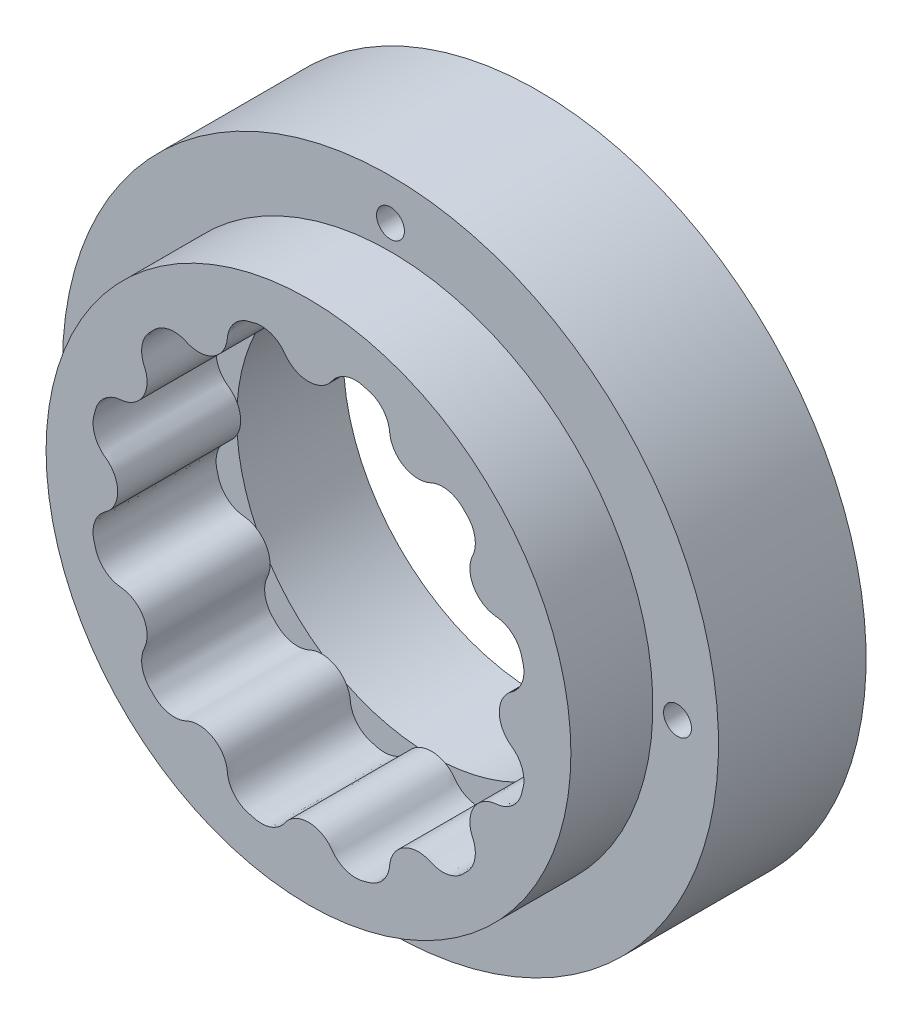
SolidWorks part; units mm, degrees
material "ABS PC"
ref_plane "Front Plane" through (0, 0, 0) normal (0, 0, 1) x (1, 0, 0)
ref_plane "Top Plane" through (0, 0, 0) normal (0, 1, 0) x (1, 0, 0)
ref_plane "Right Plane" through (0, 0, 0) normal (1, 0, 0) x (0, 0, -1)
sketch "Sketch1" plane through (0, 0, 0) normal (0, 0, 1) x (1, 0, 0)
  circle A2 centre (0, 0) radius 32
  spline S0 degree 3 poles (7.3592, -25.9621) (8.807, -25.5517) (9.7655, -24.3915) (9.8952, -22.8922) (9.8952, -22.8915) (9.8953, -22.89) (9.8955, -22.8879) (9.8956, -22.8865) (9.8957, -22.8858) (10.1265, -20.2177) (12.4458, -18.8786) (14.8718, -20.0128) (14.8725, -20.0131) (14.8738, -20.0137) (14.8757, -20.0146) (14.877, -20.0152) (14.8776, -20.0155) (16.2248, -20.6454) (17.6929, -20.4076) (18.7725, -19.3848) (18.7796, -19.3781) (18.7937, -19.3646) (18.8148, -19.3441) (18.8288, -19.3305) (18.8358, -19.3237) (19.0005, -19.1631) (19.1631, -19.0005) (19.3237, -18.8358) (19.3305, -18.8288) (19.3441, -18.8148) (19.3646, -18.7937) (19.3781, -18.7796) (19.3848, -18.7725) (20.4076, -17.6929) (20.6454, -16.2248) (20.0155, -14.8776) (20.0152, -14.877) (20.0146, -14.8757) (20.0137, -14.8738) (20.0131, -14.8725) (20.0128, -14.8718) (18.8786, -12.4458) (20.2177, -10.1265) (22.8858, -9.8957) (22.8865, -9.8956) (22.8879, -9.8955) (22.89, -9.8953) (22.8915, -9.8952) (22.8922, -9.8952) (24.3738, -9.767) (25.5263, -8.8271) (25.9499, -7.4015) (25.9526, -7.3921) (25.9581, -7.3734) (25.9661, -7.3451) (25.9714, -7.3263) (25.9741, -7.3169) (26.0365, -7.0955) (26.096, -6.8733) (26.1527, -6.6504) (26.1551, -6.641) (26.1599, -6.622) (26.1671, -6.5935) (26.1717, -6.5745) (26.174, -6.565) (26.52, -5.1187) (25.9918, -3.7284) (24.7728, -2.8766) (24.7722, -2.8762) (24.771, -2.8754) (24.7693, -2.8742) (24.7681, -2.8734) (24.7675, -2.873) (22.5723, -1.339) (22.5723, 1.339) (24.7675, 2.873) (24.7681, 2.8734) (24.7693, 2.8742) (24.771, 2.8754) (24.7722, 2.8762) (24.7728, 2.8766) (25.9918, 3.7284) (26.52, 5.1187) (26.174, 6.565) (26.1717, 6.5745) (26.1671, 6.5935) (26.1599, 6.622) (26.1551, 6.641) (26.1527, 6.6504) (26.096, 6.8733) (26.0365, 7.0955) (25.9741, 7.3169) (25.9714, 7.3263) (25.9661, 7.3451) (25.9581, 7.3734) (25.9526, 7.3921) (25.9499, 7.4015) (25.5263, 8.8271) (24.3738, 9.767) (22.8922, 9.8952) (22.8915, 9.8952) (22.89, 9.8953) (22.8879, 9.8955) (22.8865, 9.8956) (22.8858, 9.8957) (20.2177, 10.1265) (18.8786, 12.4458) (20.0128, 14.8718) (20.0131, 14.8725) (20.0137, 14.8738) (20.0146, 14.8757) (20.0152, 14.877) (20.0155, 14.8776) (20.6454, 16.2248) (20.4076, 17.6929) (19.3848, 18.7725) (19.3781, 18.7796) (19.3646, 18.7937) (19.3441, 18.8148) (19.3305, 18.8288) (19.3237, 18.8358) (19.1631, 19.0005) (19.0005, 19.1631) (18.8358, 19.3237) (18.8288, 19.3305) (18.8148, 19.3441) (18.7937, 19.3646) (18.7796, 19.3781) (18.7725, 19.3848) (17.6929, 20.4076) (16.2248, 20.6454) (14.8776, 20.0155) (14.877, 20.0152) (14.8757, 20.0146) (14.8738, 20.0137) (14.8725, 20.0131) (14.8718, 20.0128) (12.4458, 18.8786) (10.1265, 20.2177) (9.8957, 22.8858) (9.8956, 22.8865) (9.8955, 22.8879) (9.8953, 22.89) (9.8952, 22.8915) (9.8952, 22.8922) (9.767, 24.3738) (8.8271, 25.5263) (7.4015, 25.9499) (7.3921, 25.9526) (7.3734, 25.9581) (7.3451, 25.9661) (7.3263, 25.9714) (7.3169, 25.9741) (7.0955, 26.0365) (6.8733, 26.096) (6.6504, 26.1527) (6.641, 26.1551) (6.622, 26.1599) (6.5935, 26.1671) (6.5745, 26.1717) (6.565, 26.174) (5.1187, 26.52) (3.7284, 25.9918) (2.8766, 24.7728) (2.8762, 24.7722) (2.8754, 24.771) (2.8742, 24.7693) (2.8734, 24.7681) (2.873, 24.7675) (1.339, 22.5723) (-1.339, 22.5723) (-2.873, 24.7675) (-2.8734, 24.7681) (-2.8742, 24.7693) (-2.8754, 24.771) (-2.8762, 24.7722) (-2.8766, 24.7728) (-3.7284, 25.9918) (-5.1187, 26.52) (-6.565, 26.174) (-6.5745, 26.1717) (-6.5935, 26.1671) (-6.622, 26.1599) (-6.641, 26.1551) (-6.6504, 26.1527) (-6.8733, 26.096) (-7.0955, 26.0365) (-7.3169, 25.9741) (-7.3263, 25.9714) (-7.3451, 25.9661) (-7.3734, 25.9581) (-7.3921, 25.9526) (-7.4015, 25.9499) (-8.8271, 25.5263) (-9.767, 24.3738) (-9.8952, 22.8922) (-9.8952, 22.8915) (-9.8953, 22.89) (-9.8955, 22.8879) (-9.8956, 22.8865) (-9.8957, 22.8858) (-10.1265, 20.2177) (-12.4458, 18.8786) (-14.8718, 20.0128) (-14.8725, 20.0131) (-14.8738, 20.0137) (-14.8757, 20.0146) (-14.877, 20.0152) (-14.8776, 20.0155) (-16.2248, 20.6454) (-17.6929, 20.4076) (-18.7725, 19.3848) (-18.7796, 19.3781) (-18.7937, 19.3646) (-18.8148, 19.3441) (-18.8288, 19.3305) (-18.8358, 19.3237) (-19.0005, 19.1631) (-19.1631, 19.0005) (-19.3237, 18.8358) (-19.3305, 18.8288) (-19.3441, 18.8148) (-19.3646, 18.7937) (-19.3781, 18.7796) (-19.3848, 18.7725) (-20.4076, 17.6929) (-20.6454, 16.2248) (-20.0155, 14.8776) (-20.0152, 14.877) (-20.0146, 14.8757) (-20.0137, 14.8738) (-20.0131, 14.8725) (-20.0128, 14.8718) (-18.8786, 12.4458) (-20.2177, 10.1265) (-22.8858, 9.8957) (-22.8865, 9.8956) (-22.8879, 9.8955) (-22.89, 9.8953) (-22.8915, 9.8952) (-22.8922, 9.8952) (-24.3738, 9.767) (-25.5263, 8.8271) (-25.9499, 7.4015) (-25.9526, 7.3921) (-25.9581, 7.3734) (-25.9661, 7.3451) (-25.9714, 7.3263) (-25.9741, 7.3169) (-26.0365, 7.0955) (-26.096, 6.8733) (-26.1527, 6.6504) (-26.1551, 6.641) (-26.1599, 6.622) (-26.1671, 6.5935) (-26.1717, 6.5745) (-26.174, 6.565) (-26.52, 5.1187) (-25.9918, 3.7284) (-24.7728, 2.8766) (-24.7722, 2.8762) (-24.771, 2.8754) (-24.7693, 2.8742) (-24.7681, 2.8734) (-24.7675, 2.873) (-22.5723, 1.339) (-22.5723, -1.339) (-24.7675, -2.873) (-24.7681, -2.8734) (-24.7693, -2.8742) (-24.771, -2.8754) (-24.7722, -2.8762) (-24.7728, -2.8766) (-25.9918, -3.7284) (-26.52, -5.1187) (-26.174, -6.565) (-26.1717, -6.5745) (-26.1671, -6.5935) (-26.1599, -6.622) (-26.1551, -6.641) (-26.1527, -6.6504) (-26.096, -6.8733) (-26.0365, -7.0955) (-25.9741, -7.3169) (-25.9714, -7.3263) (-25.9661, -7.3451) (-25.9581, -7.3734) (-25.9526, -7.3921) (-25.9499, -7.4015) (-25.5263, -8.8271) (-24.3738, -9.767) (-22.8922, -9.8952) (-22.8915, -9.8952) (-22.89, -9.8953) (-22.8879, -9.8955) (-22.8865, -9.8956) (-22.8858, -9.8957) (-20.2177, -10.1265) (-18.8786, -12.4458) (-20.0128, -14.8718) (-20.0131, -14.8725) (-20.0137, -14.8738) (-20.0146, -14.8757) (-20.0152, -14.877) (-20.0155, -14.8776) (-20.6454, -16.2248) (-20.4076, -17.6929) (-19.3848, -18.7725) (-19.3781, -18.7796) (-19.3646, -18.7937) (-19.3441, -18.8148) (-19.3305, -18.8288) (-19.3237, -18.8358) (-19.1631, -19.0005) (-19.0005, -19.1631) (-18.8358, -19.3237) (-18.8288, -19.3305) (-18.8148, -19.3441) (-18.7937, -19.3646) (-18.7796, -19.3781) (-18.7725, -19.3848) (-17.6929, -20.4076) (-16.2248, -20.6454) (-14.8776, -20.0155) (-14.877, -20.0152) (-14.8757, -20.0146) (-14.8738, -20.0137) (-14.8725, -20.0131) (-14.8718, -20.0128) (-12.4458, -18.8786) (-10.1265, -20.2177) (-9.8957, -22.8858) (-9.8956, -22.8865) (-9.8955, -22.8879) (-9.8953, -22.89) (-9.8952, -22.8915) (-9.8952, -22.8922) (-9.767, -24.3738) (-8.8271, -25.5263) (-7.4015, -25.9499) (-7.3921, -25.9526) (-7.3734, -25.9581) (-7.3451, -25.9661) (-7.3263, -25.9714) (-7.3169, -25.9741) (-7.0955, -26.0365) (-6.8733, -26.096) (-6.6504, -26.1527) (-6.641, -26.1551) (-6.622, -26.1599) (-6.5935, -26.1671) (-6.5745, -26.1717) (-6.565, -26.174) (-5.1187, -26.52) (-3.7284, -25.9918) (-2.8766, -24.7728) (-2.8762, -24.7722) (-2.8754, -24.771) (-2.8742, -24.7693) (-2.8734, -24.7681) (-2.873, -24.7675) (-1.339, -22.5723) (1.339, -22.5723) (2.873, -24.7675) (2.8734, -24.7681) (2.8742, -24.7693) (2.8754, -24.771) (2.8762, -24.7722) (2.8766, -24.7728) (3.7386, -26.0064) (5.1488, -26.532) (6.6078, -26.1635) (6.6916, -26.1423) (6.8577, -26.0938) (7.108, -26.0267) (7.276, -25.9857) (7.3592, -25.9621) (8.807, -25.5517) (9.7655, -24.3915) knots -0.001489 0 0 0 0.022862 0.022862 0.022862 0.022874 0.022886 0.022898 0.022898 0.022898 0.055888 0.055888 0.055888 0.0559 0.055912 0.055925 0.055925 0.055925 0.078577 0.078577 0.078577 0.078746 0.078914 0.079083 0.079083 0.079083 0.083044 0.083044 0.083044 0.083213 0.083381 0.08355 0.08355 0.08355 0.106202 0.106202 0.106202 0.106215 0.106227 0.106239 0.106239 0.106239 0.139228 0.139228 0.139228 0.139241 0.139253 0.139265 0.139265 0.139265 0.161918 0.161918 0.161918 0.162087 0.162255 0.162424 0.162424 0.162424 0.166385 0.166385 0.166385 0.166553 0.166722 0.16689 0.16689 0.16689 0.189543 0.189543 0.189543 0.189555 0.189568 0.18958 0.18958 0.18958 0.222569 0.222569 0.222569 0.222581 0.222594 0.222606 0.222606 0.222606 0.245259 0.245259 0.245259 0.245427 0.245596 0.245764 0.245764 0.245764 0.249726 0.249726 0.249726 0.249894 0.250063 0.250231 0.250231 0.250231 0.272884 0.272884 0.272884 0.272896 0.272908 0.272921 0.272921 0.272921 0.30591 0.30591 0.30591 0.305922 0.305935 0.305947 0.305947 0.305947 0.3286 0.3286 0.3286 0.328768 0.328937 0.329105 0.329105 0.329105 0.333066 0.333066 0.333066 0.333235 0.333403 0.333572 0.333572 0.333572 0.356225 0.356225 0.356225 0.356237 0.356249 0.356261 0.356261 0.356261 0.389251 0.389251 0.389251 0.389263 0.389275 0.389288 0.389288 0.389288 0.41194 0.41194 0.41194 0.412109 0.412277 0.412446 0.412446 0.412446 0.416407 0.416407 0.416407 0.416576 0.416744 0.416912 0.416912 0.416912 0.439565 0.439565 0.439565 0.439578 0.43959 0.439602 0.439602 0.439602 0.472591 0.472591 0.472591 0.472604 0.472616 0.472628 0.472628 0.472628 0.495281 0.495281 0.495281 0.49545 0.495618 0.495787 0.495787 0.495787 0.499748 0.499748 0.499748 0.499916 0.500085 0.500253 0.500253 0.500253 0.522906 0.522906 0.522906 0.522918 0.522931 0.522943 0.522943 0.522943 0.555932 0.555932 0.555932 0.555944 0.555957 0.555969 0.555969 0.555969 0.578622 0.578622 0.578622 0.57879 0.578959 0.579127 0.579127 0.579127 0.583089 0.583089 0.583089 0.583257 0.583425 0.583594 0.583594 0.583594 0.606247 0.606247 0.606247 0.606259 0.606271 0.606284 0.606284 0.606284 0.639273 0.639273 0.639273 0.639285 0.639297 0.63931 0.63931 0.63931 0.661963 0.661963 0.661963 0.662131 0.662299 0.662468 0.662468 0.662468 0.666429 0.666429 0.666429 0.666598 0.666766 0.666935 0.666935 0.666935 0.689588 0.689588 0.689588 0.6896 0.689612 0.689624 0.689624 0.689624 0.722614 0.722614 0.722614 0.722626 0.722638 0.72265 0.72265 0.72265 0.745303 0.745303 0.745303 0.745472 0.74564 0.745809 0.745809 0.745809 0.74977 0.74977 0.74977 0.749938 0.750107 0.750275 0.750275 0.750275 0.772928 0.772928 0.772928 0.772941 0.772953 0.772965 0.772965 0.772965 0.805954 0.805954 0.805954 0.805967 0.805979 0.805991 0.805991 0.805991 0.828644 0.828644 0.828644 0.828812 0.828981 0.829149 0.829149 0.829149 0.833111 0.833111 0.833111 0.833279 0.833448 0.833616 0.833616 0.833616 0.856269 0.856269 0.856269 0.856281 0.856294 0.856306 0.856306 0.856306 0.889295 0.889295 0.889295 0.889307 0.88932 0.889332 0.889332 0.889332 0.911985 0.911985 0.911985 0.912153 0.912322 0.91249 0.91249 0.91249 0.916451 0.916451 0.916451 0.91662 0.916788 0.916957 0.916957 0.916957 0.93961 0.93961 0.93961 0.939622 0.939634 0.939647 0.939647 0.939647 0.972636 0.972636 0.972636 0.972648 0.97266 0.972673 0.972673 0.972673 0.995534 0.995534 0.995534 0.997023 0.998511 1 1 1 1.022862 1.022862 1.022862 weights 1 0.881989 0.881989 1 1 1 1 1 1 0.715182 0.715182 1 1 1 1 1 1 0.884361 0.884361 1 1 1 1 1 1 0.999946 0.999946 1 1 1 1 1 1 0.884361 0.884361 1 1 1 1 1 1 0.715182 0.715182 1 1 1 1 1 1 0.884361 0.884361 1 1 1 1 1 1 0.999946 0.999946 1 1 1 1 1 1 0.884361 0.884361 1 1 1 1 1 1 0.715182 0.715182 1 1 1 1 1 1 0.884361 0.884361 1 1 1 1 1 1 0.999946 0.999946 1 1 1 1 1 1 0.884361 0.884361 1 1 1 1 1 1 0.715182 0.715182 1 1 1 1 1 1 0.884361 0.884361 1 1 1 1 1 1 0.999946 0.999946 1 1 1 1 1 1 0.884361 0.884361 1 1 1 1 1 1 0.715182 0.715182 1 1 1 1 1 1 0.884361 0.884361 1 1 1 1 1 1 0.999946 0.999946 1 1 1 1 1 1 0.884361 0.884361 1 1 1 1 1 1 0.715182 0.715182 1 1 1 1 1 1 0.884361 0.884361 1 1 1 1 1 1 0.999946 0.999946 1 1 1 1 1 1 0.884361 0.884361 1 1 1 1 1 1 0.715182 0.715182 1 1 1 1 1 1 0.884361 0.884361 1 1 1 1 1 1 0.999946 0.999946 1 1 1 1 1 1 0.884361 0.884361 1 1 1 1 1 1 0.715182 0.715182 1 1 1 1 1 1 0.884361 0.884361 1 1 1 1 1 1 0.999946 0.999946 1 1 1 1 1 1 0.884361 0.884361 1 1 1 1 1 1 0.715182 0.715182 1 1 1 1 1 1 0.884361 0.884361 1 1 1 1 1 1 0.999946 0.999946 1 1 1 1 1 1 0.884361 0.884361 1 1 1 1 1 1 0.715182 0.715182 1 1 1 1 1 1 0.884361 0.884361 1 1 1 1 1 1 0.999946 0.999946 1 1 1 1 1 1 0.884361 0.884361 1 1 1 1 1 1 0.715182 0.715182 1 1 1 1 1 1 0.884361 0.884361 1 1 1 1 1 1 0.999946 0.999946 1 1 1 1 1 1 0.884361 0.884361 1 1 1 1 1 1 0.715182 0.715182 1 1 1 1 1 1 0.881989 0.881989 1 1 1 1 1 1 0.881989 0.881989 only from (7.3592, -25.9621) to (7.3592, -25.9621)
  dimension "D1" = 64
extrude "Boss-Extrude1" add sketch "Sketch1" along normal blind 15
sketch "Sketch3" plane through (0, 0, 0) normal (0, 0, -1) x (-1, 0, 0)
  circle A0 centre (0, 0) radius 30
  circle A1 centre (0, 0) radius 40
  dimension "D1" = 80
extrude "Boss-Extrude3" add sketch "Sketch3" against normal blind 5
sketch "Sketch4" plane through (0, 0, 0) normal (0, 0, -1) x (-1, 0, 0)
  circle A0 centre (0, 0) radius 40
  circle A1 centre (0, 0) radius 23.75
  dimension "D1" = 47.5
extrude "Boss-Extrude4" add sketch "Sketch4" along normal blind 13
sketch "Sketch5" plane through (0, 0, -13) normal (0, 0, -1) x (-1, 0, 0)
  circle A0 centre (0, 35) radius 1.7
  circle A2 centre (35, 0) radius 1.7
  circle A4 centre (0, -35) radius 1.7
  circle A6 centre (-35, 0) radius 1.7
  circle A8 centre (24.7487, 24.7487) radius 1.7 [skipped]
  circle A9 centre (24.7487, -24.7487) radius 1.7 [skipped]
  circle A10 centre (-24.7487, -24.7487) radius 1.7 [skipped]
  circle A11 centre (-24.7487, 24.7487) radius 1.7 [skipped]
  point P19 (0, 0)
  dimension "D2" = 3.4
  dimension "D1" = 35
  dimension "D3" = 8
extrude "Cut-Extrude1" cut sketch "Sketch5" against normal blind 20
sketch "Sketch6" plane through (0, 0, -13) normal (0, 0, -1) x (-1, 0, 0)
  circle A0 centre (0, 35) radius 3.125
  circle A1 centre (35, 0) radius 3.125
  circle A2 centre (0, -35) radius 3.125
  circle A3 centre (-35, 0) radius 3.125
  point P12 (0, 0)
  dimension "D1" = 6.25
  dimension "D2" = 4
extrude "Cut-Extrude2" [suppressed] cut sketch "Sketch6" against normal blind 3
